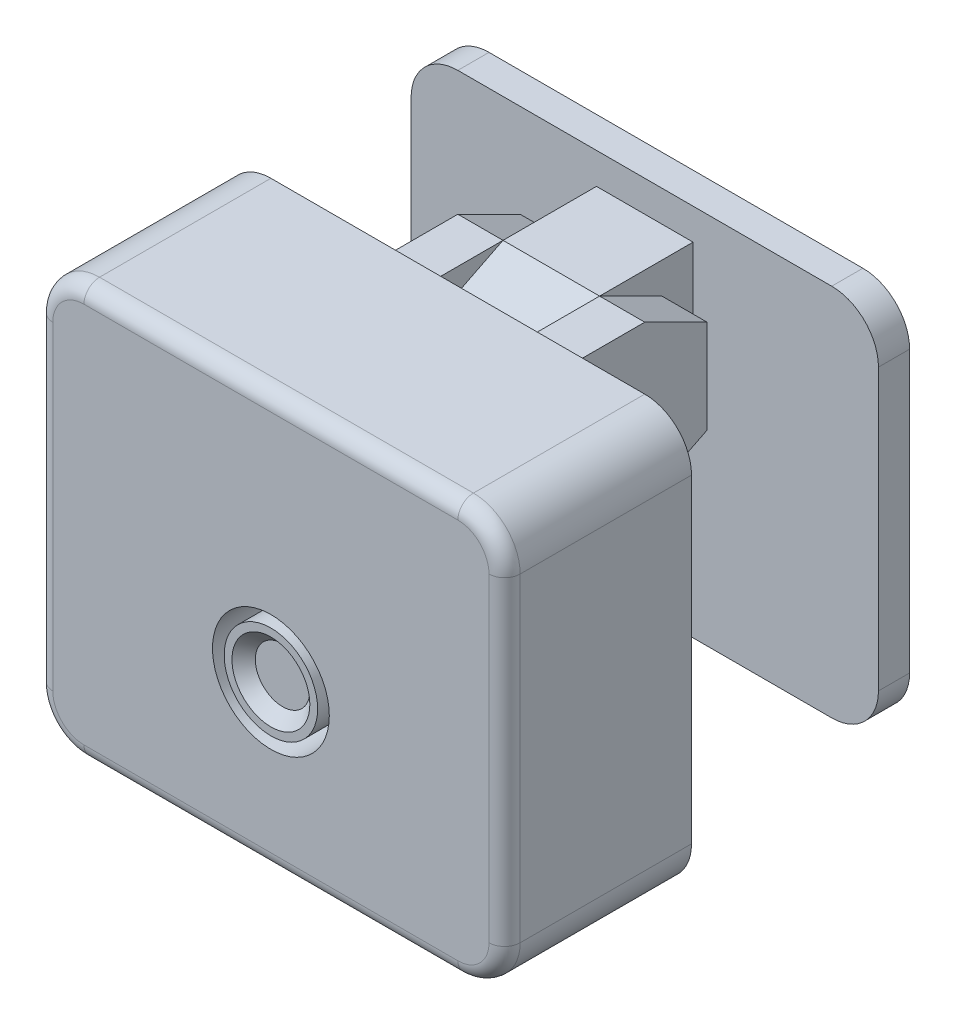
SolidWorks part; units mm, degrees
ref_plane "Front Plane" through (0, 0, 0) normal (0, 0, 1) x (1, 0, 0)
ref_plane "Top Plane" through (0, 0, 0) normal (0, 1, 0) x (1, 0, 0)
ref_plane "Right Plane" through (0, 0, 0) normal (1, 0, 0) x (0, 0, -1)
sketch "Sketch1" plane through (0, 0, 0) normal (0, 0, 1) x (1, 0, 0)
  line L1 (-15, -13.25) -> (15, -13.25)
  line L2 (-15, -13.25) -> (-15, 13.25)
  line L3 (-15, 13.25) -> (15, 13.25)
  line L4 (15, -13.25) -> (15, 13.25)
  line L5 (-15, -13.25) -> (15, 13.25) construction
  line L6 (-15, 13.25) -> (15, -13.25) construction
  point P0 (0, 0)
  dimension "D1" = 26.5
  dimension "D2" = 30
extrude "Boss-Extrude1" add sketch "Sketch1" along normal blind 12 contours L3 L4 L1 L2
fillet "Fillet1" radius 3 4 edges at (15, -13.25, 6) (-15, -13.25, 6) (15, 13.25, 6) (-15, 13.25, 6)
fillet "Fillet2" radius 1 8 edges at (-14.1213, -12.3713, 12) (-15, 0, 12) (-14.1213, 12.3713, 12) (0, 13.25, 12) (14.1213, 12.3713, 12) (15, 0, 12) (14.1213, -12.3713, 12) (0, -13.25, 12)
sketch "Sketch2" plane through (0, 0, 12) normal (0, 0, 1) x (1, 0, 0)
  line L0 (0, -13.25) -> (0, -2.75) construction
  line L1 (12, -13.25) -> (-12, -13.25) construction
  circle A0 centre (0, -2.75) radius 3.75
  dimension "D2" = 7.5
  dimension "D1" = 10.5
extrude "Cut-Extrude1" cut sketch "Sketch2" against normal blind 5
sketch "Sketch3" plane through (0, 0, 7) normal (0, 0, 1) x (1, 0, 0)
  circle A0 centre (0, -2.75) radius 3
  dimension "D1" = 6
extrude "Boss-Extrude2" add sketch "Sketch3" along normal blind 5
sketch "Sketch4" plane through (0, 0, 12) normal (0, 0, 1) x (1, 0, 0)
  circle A0 centre (0, -2.75) radius 1.75
  dimension "D1" = 3.5
extrude "Cut-Extrude2" cut sketch "Sketch4" against normal blind 0.75
chamfer "Chamfer1" distance 0.75 angle 45 1 edges at (1.75, -2.75, 12)
sketch "Sketch5" plane through (0, 0, 0) normal (0, 0, -1) x (-1, 0, 0)
  line L0 (0, 13.25) -> (0, -13.25) construction
  line L1 (-6, 11.25) -> (-3.1, 11.25)
  line L2 (-6, 11.25) -> (-6, 1.25)
  line L3 (-6, 1.25) -> (-3.1, 1.25)
  line L4 (-3.1, 11.25) -> (-3.1, 1.25)
  line L5 (12, 13.25) -> (-12, 13.25) construction
  line L6 (12, -13.25) -> (-12, -13.25) construction
  line L7 (6, 1.25) -> (3.1, 1.25)
  line L8 (3.1, 11.25) -> (3.1, 1.25)
  line L9 (6, 11.25) -> (3.1, 11.25)
  line L10 (6, 11.25) -> (6, 1.25)
  dimension "D1" = 2
  dimension "D2" = 2.9
  dimension "D3" = 10
  dimension "D4" = 3.1
extrude "Boss-Extrude3" add sketch "Sketch5" along normal blind 10
chamfer "Chamfer2" distance 4 distance2 2 4 edges at (4.55, 1.25, -10) (-4.55, 1.25, -10) (-4.55, 11.25, -10) (4.55, 11.25, -10) first distance on face at (4.55, 1.25, -5) first distance on face at (-4.55, 1.25, -5) first distance on face at (-4.55, 11.25, -5) first distance on face at (4.55, 11.25, -5)
sketch "Sketch6" plane through (-3.1, 0, 0) normal (1, 0, 0) x (0, 0, -1)
  line L0 (2, 9.25) -> (2, 3.25)
  line L3 (10, 9.25) -> (10, 3.25) construction
  line L4 (2, 9.25) -> (6, 11.25)
  line L5 (6, 11.25) -> (12, 11.25)
  line L6 (12, 11.25) -> (12, 1.25)
  line L7 (12, 1.25) -> (6, 1.25)
  line L8 (6, 1.25) -> (2, 3.25)
  line L9 (6, 11.25) -> (0, 11.25) construction
  line L10 (6, 1.25) -> (0, 1.25) construction
  point P0 (2, 9.5576)
  point P11 (12, 1.25)
  dimension "D1" = 8
  dimension "D2" = 2
  dimension "D3" = 6
  dimension "D4" = 2
extrude "Boss-Extrude4" add sketch "Sketch6" along normal up to surface (6.2 mm away) up to face at (3.1, 6.25, -5.3333)
sketch "Sketch7" plane through (0, 0, -12) normal (0, 0, -1) x (-1, 0, 0)
  line L0 (0, 11.25) -> (0, 1.25) construction
  line L1 (-3.1, 11.25) -> (3.1, 11.25) construction
  line L2 (-3.1, 1.25) -> (3.1, 1.25) construction
  line L4 (-15, -10.75) -> (15, -10.75)
  line L5 (-15, -10.75) -> (-15, 13.25)
  line L6 (-15, 13.25) -> (15, 13.25)
  line L7 (15, -10.75) -> (15, 13.25)
  line L8 (-15, -10.75) -> (15, 13.25) construction
  line L9 (-15, 13.25) -> (15, -10.75) construction
  point P6 (0, 1.25)
  dimension "D1" = 24
  dimension "D2" = 30
  dimension "D3" = 2
extrude "Boss-Extrude5" add sketch "Sketch7" along normal blind 2
fillet "Fillet3" radius 3 4 edges at (15, -10.75, -13) (15, 13.25, -13) (-15, -10.75, -13) (-15, 13.25, -13)
sketch "Sketch8" plane through (0, 0, 0) normal (0, 0, -1) x (-1, 0, 0)
  line L0 (-11.5, -13.25) -> (-11.5, -5.75)
  line L1 (12, -13.25) -> (-12, -13.25) construction
  line L2 (-11.5, -5.75) -> (11.5, -5.75)
  line L3 (11.5, -5.75) -> (11.5, -13.25)
  line L4 (11.5, -13.25) -> (-11.5, -13.25)
  line L5 (0, -13.25) -> (0, 0)
  line M6 (-12, -13.25) -> (12, -13.25)
  dimension "D1" = 7.5
  dimension "D2" = 23
extrude "Cut-Extrude3" cut sketch "Sketch8" against normal blind 5 contours L5 L4 L3 L2 | L5 L2 L0 M6 region at (5.75, -9.5, 0) region at (-5.75, -9.5, 0)
